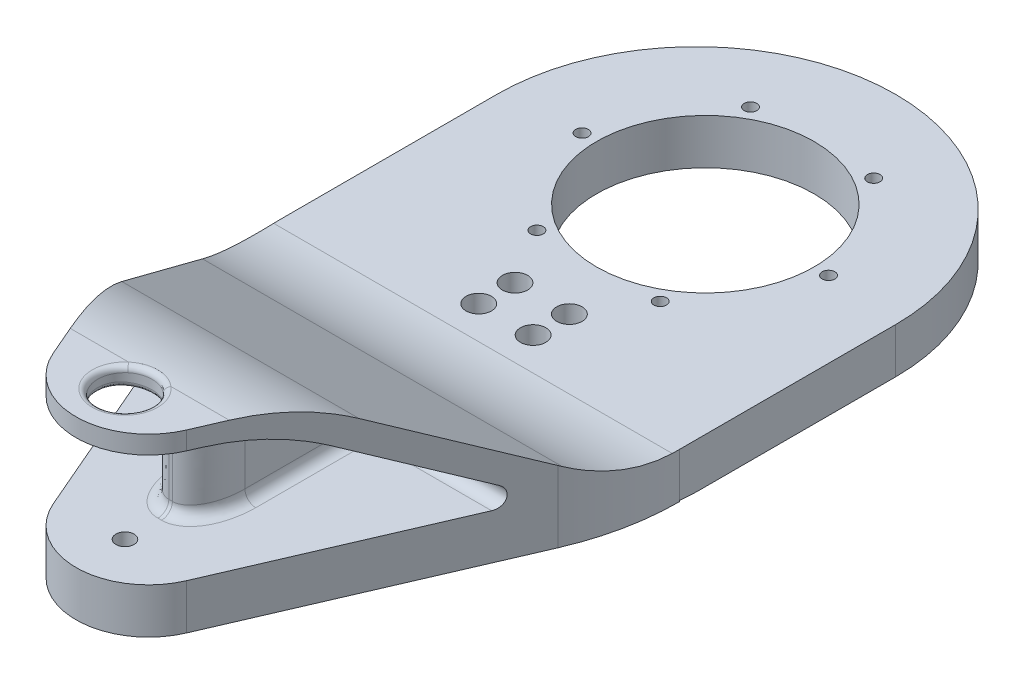
SolidWorks part; units mm, degrees
ref_plane "Plan de face" through (0, 0, 0) normal (0, 0, 1) x (1, 0, 0)
ref_plane "Plan de dessus" through (0, 0, 0) normal (0, 1, 0) x (1, 0, 0)
ref_plane "Plan de droite" through (0, 0, 0) normal (1, 0, 0) x (0, 0, -1)
sketch "Esquisse1" plane through (0, 0, 0) normal (0, 1, 0) x (1, 0, 0)
  line L0 (55, 105) -> (55, -70) construction
  line L1 (0, 0) -> (110, 0)
  line L2 (0, 0) -> (0, 105)
  line L3 (0, 105) -> (110, 105)
  line L4 (110, 0) -> (110, 105)
  dimension "D1" = 110
  dimension "D2" = 105
extrude "Boss.-Extru.1" add sketch "Esquisse1" along normal blind 12.5
sketch "Esquisse2" plane through (0, 12.5, 0) normal (0, 1, 0) x (1, 0, 0)
  line L0 (55, 105) -> (55, 0) construction
  line L1 (110, 105) -> (0, 105) construction
  line L2 (0, 0) -> (110, 0) construction
  line L3 (0, 52.5) -> (110, 52.5) construction
  line L4 (0, 105) -> (0, 0) construction
  line L5 (110, 0) -> (110, 105) construction
  circle A0 centre (89, 52.5) radius 1.75
  circle A10 centre (55, 52.5) radius 30
  circle A15 centre (72, 23.0551) radius 1.75
  circle A16 centre (38, 23.0551) radius 1.75
  circle A17 centre (21, 52.5) radius 1.75
  circle A18 centre (38, 81.9449) radius 1.75
  circle A19 centre (72, 81.9449) radius 1.75
  point P14 (55, 52.5)
  point P28 (55, 52.5)
  dimension "D1" = 3.5
  dimension "D2" = 6
  dimension "D3" = 60
  dimension "D4" = 34
extrude "Enlèv. mat.-Extru.1" cut sketch "Esquisse2" against normal through all
ref_plane "Plan1" through (0, 46, 0) normal (0, 1, 0) x (1, 0, 0)
sketch "Esquisse4" plane through (110, 0, 0) normal (1, 0, 0) x (0, 0, -1)
  line L0 (0, 12.5) -> (-11.6025, 12.5)
  line L1 (-36.6025, 19.1987) -> (-75.7513, 41.8013)
  line L3 (-81.091, 36.8013) -> (-28.9519, 6.6987)
  line L4 (-3.9519, 0) -> (0, 0)
  line L5 (0, 0) -> (0, 12.5)
  line L6 (20.9498, 46) -> (-97.6073, 46) construction
  line L7 (-25, 12.5) -> (-25, 0) construction
  line L8 (60.5, 46) -> (-60.5, 46) construction
  line L9 (0, 12.5) -> (105, 12.5) construction
  line L10 (-106.091, 43.5) -> (-121.091, 43.5)
  line L11 (-121.091, 43.5) -> (-121.091, 48.5)
  line L12 (-121.091, 48.5) -> (-100.7513, 48.5)
  arc A0 (-11.6025, 12.5) -> (-36.6025, 19.1987) centre (-11.6025, 62.5) cw
  arc A1 (-28.9519, 6.6987) -> (-3.9519, 0) centre (-3.9519, 50) ccw
  arc A2 (-81.091, 36.8013) -> (-106.091, 43.5) centre (-106.091, -6.5) ccw
  arc A3 (-75.7513, 41.8013) -> (-100.7513, 48.5) centre (-100.7513, -1.5) ccw
  point P9 (-121.091, 46)
  point P25 (-92.6936, 43.5)
  dimension "D6" = 50
  dimension "D7" = 50
  dimension "D8" = 50
  dimension "D9" = 50
  dimension "D1" = 7
  dimension "D2" = 25
  dimension "D3" = 150
  dimension "D4" = 5
  dimension "D5" = 15
extrude "Boss.-Extru.2" add sketch "Esquisse4" against normal up to surface (110 mm away) up to face at (0, 6.25, -52.5)
sketch "Esquisse5" plane through (0, 48.5, 0) normal (0, 1, 0) x (1, 0, 0)
  line L0 (5.7274, -37.3768) -> (36.6364, -109.0143)
  line L1 (0, -11.6025) -> (0, -36.6025) construction
  line L2 (0, -121.091) -> (110, -121.091) construction
  line L5 (0, -75.7513) -> (0, -36.6025) construction
  line L8 (0, -11.6025) -> (0, -9.6454)
  line L9 (0, -11.6025) -> (-10, -11.6025)
  line L10 (-10, -11.6025) -> (-10, -131.091)
  line L11 (-10, -131.091) -> (120, -131.091)
  line L14 (55, -1.6025) -> (55, -186.4393) construction
  line L15 (120, -11.6025) -> (120, -131.091)
  line L16 (110, -11.6025) -> (120, -11.6025)
  line L17 (110, -11.6025) -> (110, -9.6454)
  line L18 (104.2726, -37.3768) -> (73.3636, -109.0143)
  arc A0 (36.6364, -109.0143) -> (73.3636, -109.0143) centre (55, -101.091) ccw
  arc A1 (0, -9.6454) -> (5.7274, -37.3768) centre (70, -9.6454) ccw
  arc A2 (110, -9.6454) -> (104.2726, -37.3768) centre (40, -9.6454) cw
  point P8 (55, -121.091)
  point P17 (46.17, -121.091)
  point P23 (0, -24.1025)
  point P28 (55, -131.091)
  point P30 (110, -24.1025)
  dimension "D1" = 20
  dimension "D4" = 70
  dimension "D2" = 10
  dimension "D3" = 10
extrude "Enlèv. mat.-Extru.2" cut sketch "Esquisse5" against normal through all
sketch "Esquisse6" plane through (0, 48.5, 0) normal (0, 1, 0) x (1, 0, 0)
  line L0 (55, -121.091) -> (55, -11.6025) construction
  line L1 (0.0274, -11.6025) -> (109.9726, -11.6025) construction
  arc A0 (36.6364, -109.0143) -> (73.3636, -109.0143) centre (55, -101.091) ccw construction
  circle A1 centre (55, -107.591) radius 7.5
  dimension "D1" = 15
  dimension "D2" = 13.5
extrude "Enlèv. mat.-Extru.3" cut sketch "Esquisse6" against normal through all contours A1
ref_plane "Plan2" through (55, 0, 0) normal (-1, 0, 0) x (0, 0, 1)
fillet "Congé6" radius 55 2 edges at (0, 6.25, -105) (110, 6.25, -105)
sketch "Esquisse8" plane through (0, 0, 0) normal (0, -1, 0) x (1, 0, 0)
  line L7 (0, 9.6454) -> (110, 9.6454)
  line L10 (104.2726, 37.3768) -> (73.3636, 109.0143)
  line L13 (36.6364, 109.0143) -> (5.7274, 37.3768)
  circle A6 centre (55, 107.591) radius 2.5
  arc A7 (36.6364, 109.0143) -> (73.3636, 109.0143) centre (55, 101.091) cw
  arc A8 (104.2726, 37.3768) -> (110, 9.6454) centre (40, 9.6454) cw
  arc A9 (5.7274, 37.3768) -> (0, 9.6454) centre (70, 9.6454) ccw
  dimension "D1" = 5
extrude "Boss.-Extru.5" add sketch "Esquisse8" against normal blind 12.5
sketch "Esquisse9" plane through (55, 0, 0) normal (-1, 0, 0) x (0, 0, 1)
  line L5 (39, 12.5) -> (95, 44.8316)
  line L9 (39, 12.5) -> (81.091, 36.8013) construction
  line L10 (39, 12.5) -> (95, 12.5)
  line L11 (95, 12.5) -> (95, 44.8316)
  dimension "D1" = 56
extrude "Boss.-Extru.6" add sketch "Esquisse9" along normal blind 7.5 and the other way blind 7.5
fillet "Congé8" radius 3 2 edges at (83.0361, 12.5, 39) (26.9639, 12.5, 39)
fillet "Congé9" radius 7 1 edges at (47.5, 27.3772, 95) second distance 13 first distance on face at (55, 27.3772, 95)
fillet "Congé10" radius 13 1 edges at (62.5, 27.3772, 95) second distance 7 first distance on face at (62.5, 24.4201, 73.5261)
fillet "Congé11" radius 3 14 edges at (47.5, 27.4497, 64.8936) (62.5, 27.4497, 64.8936) (47.5, 14.7235, 47.2984) (62.5, 14.7235, 47.2984)
sketch "Esquisse10" plane through (0, 12.5, 0) normal (0, 1, 0) x (1, 0, 0)
  line L0 (55, 105) -> (55, -121.091) construction
  line L2 (47.5, 7.5) -> (62.5, 7.5) construction
  line L3 (47.5, 7.5) -> (47.5, -2.5) construction
  line L4 (47.5, -2.5) -> (62.5, -2.5) construction
  line L5 (62.5, 7.5) -> (62.5, -2.5) construction
  arc A0 (36.6364, -109.0143) -> (73.3636, -109.0143) centre (55, -101.091) ccw construction
  circle A1 centre (55, 52.5) radius 30 construction
  circle A2 centre (47.5, 7.5) radius 3.5
  circle A3 centre (62.5, 7.5) radius 3.5
  circle A4 centre (62.5, -2.5) radius 3.5
  circle A5 centre (47.5, -2.5) radius 3.5
  point P10 (55, -2.5)
  dimension "D4" = 7
  dimension "D1" = 10
  dimension "D2" = 15
  dimension "D3" = 45
extrude "Enlèv. mat.-Extru.4" cut sketch "Esquisse10" against normal blind 8.5
sketch "Esquisse11" plane through (0, 12.5, 0) normal (0, 1, 0) x (1, 0, 0)
  circle A0 centre (47.5, 7.5) radius 1.7
  circle A1 centre (62.5, 7.5) radius 1.7
  circle A2 centre (62.5, -2.5) radius 1.7
  circle A3 centre (47.5, -2.5) radius 1.7
  point P0 (47.5, 7.5)
  point P1 (62.5, 7.5)
  point P3 (62.5, -2.5)
  point P5 (47.5, -2.5)
  dimension "D1" = 3.4
extrude "Enlèv. mat.-Extru.5" cut sketch "Esquisse11" against normal through all
fillet "Congé12" radius 0.1 4 edges at (62.5, 4, -5.8) (62.5, 4, 4.2) (47.5, 4, 4.2) (47.5, 4, -5.8) profile chamfer
sketch "Esquisse12" plane through (0, 0, 0) normal (0, -1, 0) x (1, 0, 0)
  circle A0 centre (72, -23.0551) radius 3.5
  circle A1 centre (89, -52.5) radius 3.5
  circle A2 centre (38, -23.0551) radius 3.5
  circle A3 centre (21, -52.5) radius 3.5
  circle A4 centre (38, -81.9449) radius 3.5
  circle A5 centre (72, -81.9449) radius 3.5
  point P0 (38, -23.0551)
  point P1 (72, -23.0551)
  point P3 (89, -52.5)
  point P5 (72, -81.9449)
  point P7 (38, -81.9449)
  point P9 (21, -52.5)
  dimension "D1" = 7
extrude "Enlèv. mat.-Extru.6" cut sketch "Esquisse12" against normal blind 8.5
chamfer "Chanfrein1" distance 0.1 angle 45 6 edges at (89, 8.5, -54.25) (72, 8.5, -83.6949) (38, 8.5, -83.6949) (21, 8.5, -54.25) (38, 8.5, -24.8051) (72, 8.5, -24.8051)
fillet "Congé14" radius 1.5 4 edges at (55, 43.5, 115.091) (54.8285, 43.1389, 100.093)
